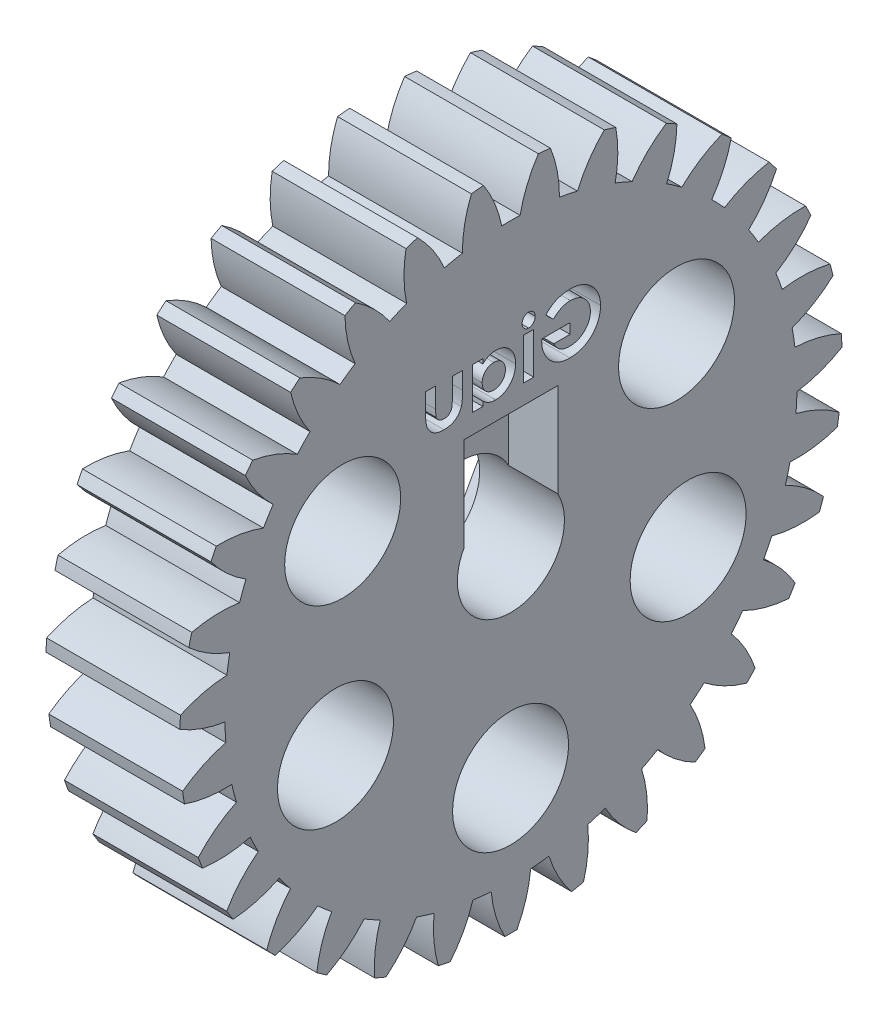
SolidWorks part; units mm, degrees
ref_plane "Plane1" through (0, 0, 0) normal (0, 0, 1) x (1, 0, 0)
ref_plane "Plane2" through (0, 0, 0) normal (0, 1, 0) x (1, 0, 0)
ref_plane "Plane3" through (0, 0, 0) normal (1, 0, 0) x (0, 0, -1)
sketch "HoldingSke" plane through (0, 0, 0) normal (0, 1, 0) x (1, 0, 0)
  line L0 (0, 0) -> (0.381, -0.2289)
  line L1 (-15, 0) -> (100, 0) construction
  line L2 (0, 0) -> (-2.1039, 2.3779)
  line L3 (0, 0) -> (-11.863, 4.5341)
  line L4 (0, 0) -> (7.4025, 4.4479)
  line L5 (0, 0) -> (-46.8476, -17.4728)
  line L6 (0, 0) -> (-12.4344, -8.3896)
  line L7 (-2.1039, 2.3779) -> (8.6586, 51.2059)
  line L8 (-76.2, 54.61) -> (-76.1, 54.61)
  line L9 (-71.009, 38.7566) -> (-53.1078, 45.2721)
  line L10 (-76.2, 71.12) -> (104.1128, 71.12)
  line L11 (0, 0) -> (-15, 0)
  line L12 (-76.2, 101.6) -> (-76.123, 101.6)
  line L13 (24.9733, 27.94) -> (52.9518, 28.4284)
  line L14 (24.9733, 27.94) -> (24.9743, 27.94)
  line L15 (24.9733, 27.94) -> (100.4006, 29.5858)
  line L16 (-63.627, -2.25) -> (-12.827, -2.25)
  circle A0 centre (0, 0) radius 0.4
  circle A1 centre (0, 0) radius 32.0615
  circle A2 centre (0, 0) radius 37.5
  circle A3 centre (0, 0) radius 0.4
  dimension "MHD" = 64.123
  dimension "Hub_dia" = 75
  dimension "Bore" = 0.8
  dimension "MBD" = 0.8
  dimension "Num_teeth" = 31
  dimension "Pitch_radius" = 180.3128
  dimension "Pitch" = 0.4444
  dimension "Width" = 15
  dimension "Overall_len" = 50
  dimension "Show_teeth" = 31
  dimension "Thickness" = 15
  dimension "OAL" = 50.0001
  dimension "T_dim" = 0.1
  dimension "Ap" = 20
  dimension "H" = 19.05
  dimension "Backlash" = 0.077
  dimension "Addendum_fac" = 1
  dimension "Dedendum_fac" = 1.25
  dimension "Clearance_fac" = 0.25
  dimension "Dedendum_add" = 0.001
  dimension "Module" = 2.25
sketch "BasProSke" plane through (0, 0, 0) normal (0, 1, 0) x (1, 0, 0)
  line L0 (-10, 0) -> (60, 0) construction
  line L1 (0, 0) -> (0, 37.125)
  line L2 (0, 0) -> (15, 0)
  line L3 (15, 0) -> (15, 37.125)
  line L4 (15, 37.125) -> (0, 37.125)
  dimension "Diameter" = 74.25
  dimension "Thickness" = 15
revolve "Base-Revolve" add sketch "BasProSke" angle 360 about L0
sketch "TooCutSke" plane through (0, 0, 0) normal (1, 0, 0) x (0, 0, -1)
  line L1 (0, 0) -> (0, 107) construction
  line L2 (0, 0) -> (-1.9011, 34.8231) construction
  line L3 (0, 0) -> (-7.0488, 69.3161) construction
  line L4 (-1.9011, 34.8231) -> (-3.5244, 34.6581) construction
  arc A0 (1.0309, 32.0449) -> (-1.0309, 32.0449) centre (0, 0) ccw
  arc A1 (3.0958, 37.0212) -> (-3.0958, 37.0212) centre (0, 0) ccw
  circle A2 centre (0, 0) radius 34.875 construction
  circle A3 centre (0, 0) radius 32.7718 construction
  arc A4 (-1.0309, 32.0449) -> (-3.0958, 37.0212) centre (-14.7056, 29.2871) ccw
  arc A5 (3.0958, 37.0212) -> (1.0309, 32.0449) centre (14.7056, 29.2871) ccw
  dimension "Root_dia" = 64.123
  dimension "Overcut_dia" = 74.3008
  dimension "Pitch_dia" = 69.75
  dimension "Base_dia" = 65.5436
  dimension "Flank_rad" = 13.95
  dimension "Half_ang" = 5.806
  dimension "Half_CT" = 1.6316
extrude "ToothCut" cut sketch "TooCutSke" along normal through all
fillet "Breaks" [suppressed] radius 0.045 tangent propagation no
fillet "RootFillets" [suppressed] radius 0.5635
pattern_circular "TeethCuts" count 31 over 360 about axis through (-10, 0, 0) along (1, 0, 0) of "ToothCut", "RootFillets", "Breaks"
sketch "HubNeaOneSke" plane through (0, 0, 0) normal (-1, 0, 0) x (0, 0, 1)
  circle A0 centre (0, 0) radius 32.0615
  dimension "Diameter" = 64.123
extrude "HubNearOne" [suppressed] add sketch "HubNeaOneSke" along normal blind 35.0001
sketch "HubNeaBotSke" plane through (0, 0, 0) normal (-1, 0, 0) x (0, 0, 1)
  circle A0 centre (0, 0) radius 32.0615
  dimension "Diameter" = 64.123
extrude "HubNearBoth" [suppressed] add sketch "HubNeaBotSke" along normal blind 17.5
ref_plane "FarPln" through (15, 0, 0) normal (1, 0, 0) x (0, 0, -1)
sketch "HubFarSke" plane through (15, 0, 0) normal (1, 0, 0) x (0, 0, -1)
  circle A0 centre (0, 0) radius 32.0615
  dimension "Diameter" = 64.123
extrude "HubFar" [suppressed] add sketch "HubFarSke" along normal blind 17.5
sketch "BorSke" plane through (0, 0, 0) normal (1, 0, 0) x (0, 0, -1)
  circle A0 centre (0, 0) radius 6
  dimension "Diameter" = 12
extrude "Bore" cut sketch "BorSke" along normal mid plane 100.0001
sketch "KeySke" plane through (0, 0, 0) normal (1, 0, 0) x (0, 0, -1)
  line L0 (-0.05, 0) -> (-0.05, 0.5)
  line L1 (-0.05, 0.5) -> (0.05, 0.5)
  line L2 (0.05, 0.5) -> (0.05, 0)
  line L3 (0, 0) -> (0, 34) construction
  line L4 (-0.05, 0) -> (0.05, 0)
  dimension "Offset" = 0.5
  dimension "Width" = 0.1
extrude "Keyway" [suppressed] cut sketch "KeySke" along normal mid plane 100.0001
pattern_circular "Keyway2" [suppressed] count 2 every 90 about axis through (-10, 0, 0) along (1, 0, 0)
sketch "Sketch1" plane through (0, 0, 0) normal (-1, 0, 0) x (0, 0, 1)
  text T0 "<b>Giau</b>\r\n\r\n" font "Century Gothic" height 6.35
sketch "Sketch2" plane through (15, 0, 0) normal (1, 0, 0) x (0, 0, -1)
  line L2 (-5.25, 2.9047) -> (-5.25, 13.4047)
  line L3 (-5.25, 13.4047) -> (5.25, 13.4047)
  line L4 (5.25, 2.9047) -> (5.25, 13.4047)
  arc A0 (-5.25, 2.9047) -> (5.25, 2.9047) centre (0, 0) ccw
  circle A1 centre (0, 0) radius 6 construction
  dimension "D1" = 0
  dimension "D5" = 10.5
  dimension "D6" = 10.5
extrude "Cut-Extrude1" cut sketch "Sketch2" against normal blind 5.5
extrude "Cut-Extrude3" cut sketch "Sketch1" against normal through all
sketch "Sketch7" plane through (0, 0, 0) normal (-1, 0, 0) x (0, 0, 1)
sketch "Sketch8" plane through (0, 0, 0) normal (-1, 0, 0) x (0, 0, 1)
  line L1 (13.854, -0.2947) -> (7.1504, 11.8322)
  line L2 (7.1504, 11.8322) -> (-6.7036, 12.0901)
  line L3 (-6.7036, 12.0901) -> (-13.854, 0.2211)
  line L4 (-13.854, 0.2211) -> (-7.1504, -11.9057)
  line L5 (-7.1504, -11.9057) -> (6.7036, -12.1637)
  line L6 (6.7036, -12.1637) -> (13.854, -0.2947)
  circle A0 centre (0, -0.0368) radius 12 construction
  circle A1 centre (0, 0) radius 6 construction
  dimension "D1" = 0
  dimension "D2" = 24
extrude "Cut-Extrude5" cut sketch "Sketch8" against normal blind 5.5
sketch "Sketch10" plane through (0, 0, 0) normal (-1, 0, 0) x (0, 0, 1)
  line L0 (-6.7036, 12.0901) -> (-13.854, 0.2211) construction
  line L1 (13.854, -0.2947) -> (7.1504, 11.8322) construction
  line L2 (6.7036, -12.1637) -> (13.854, -0.2947) construction
  line L3 (-7.1504, -11.9057) -> (6.7036, -12.1637) construction
  line L4 (-13.854, 0.2211) -> (-7.1504, -11.9057) construction
  circle A0 centre (-19.8634, -9.5779) radius 6.5
  circle A1 centre (0.0405, -22.0413) radius 6.5
  circle A2 centre (19.6658, -10.0262) radius 6.5
  circle A3 centre (18.8582, 11.3227) radius 6.5
  circle A4 centre (-18.5625, 11.7841) radius 6.5
  dimension "D6" = 13
  dimension "D7" = 13
  dimension "D8" = 13
  dimension "D9" = 13
  dimension "D10" = 13
  dimension "D1" = 10
  dimension "D2" = 10
  dimension "D3" = 10
  dimension "D4" = 10
  dimension "D5" = 10
extrude "Cut-Extrude6" cut sketch "Sketch10" against normal through all
equation "' \"Module@HoldingSke\" = 6.35"
equation "' \"Num_teeth@HoldingSke\" = 12"
equation "' \"Ap@HoldingSke\" =  20"
equation "' \"Width@HoldingSke\" = 0.5 * 25.4"
equation "' \"Hub_dia@HoldingSke\"= 1 * 25.4"
equation "' \"Overall_len@HoldingSke\" = 1.0 * 25.4"
equation "' \"Bore@HoldingSke\" = 0.75 * 25.4"
equation "' \"T_dim@HoldingSke\" = 0.1 * 25.4"
equation "' \"Width@KeySke\" = 0.25 * 25.4"
equation "' \"Show_teeth@HoldingSke\" = 13"
equation "' \"Backlash@HoldingSke\" = 0.009 * 25.4"
equation "' \"Addendum_fac@HoldingSke\" = 1.0"
equation "' \"Dedendum_fac@HoldingSke\" = 1.25"
equation "' \"Dedendum_add@HoldingSke\" = 0.00005 * 25.4"
equation "' \"Clearance_fac@HoldingSke\" = 0.25"
equation "\"Pitch@HoldingSke\" = 1 / \"Module@HoldingSke\""
equation "\"Overcut_dia@TooCutSke\" = (\"Num_teeth@HoldingSke\" + 2 * \"Addendum_fac@HoldingSke\") / \"Pitch@HoldingSke\" + 0.002 * 25.4"
equation "\"Pitch_dia@TooCutSke\" = \"Num_teeth@HoldingSke\" / \"Pitch@HoldingSke\""
equation "\"Base_dia@TooCutSke\" = \"Num_teeth@HoldingSke\" / \"Pitch@HoldingSke\" * cos((\"Ap@HoldingSke\"  * 3.14159265 / 180))"
equation "\"Root_dia@TooCutSke\" = (\"Num_teeth@HoldingSke\" + 2) / \"Pitch@HoldingSke\" - 2 * (\"Addendum_fac@HoldingSke\" + \"Dedendum_fac@HoldingSke\") / \"Pitch@HoldingSke\" - \"Dedendum_add@HoldingSke\" * 2"
equation "\"Half_ang@TooCutSke\" = 180 / \"Num_teeth@HoldingSke\""
equation "\"Half_CT@TooCutSke\" = \"Num_teeth@HoldingSke\" / \"Pitch@HoldingSke\" * sin((3.14159265 / 2 / \"Num_teeth@HoldingSke\")) / 2 - 7 * \"Backlash@HoldingSke\" / 4"
equation "\"Flank_rad@TooCutSke\" = \"Num_teeth@HoldingSke\" / \"Pitch@HoldingSke\" / 5"
equation "\"Radius@RootFillets\" = \"Clearance_fac@HoldingSke\" / \"Pitch@HoldingSke\" + \"Dedendum_add@HoldingSke\""
equation "\"Break_rad@Breaks\" = 0.02 / \"Pitch@HoldingSke\""
equation "\"Thickness@HoldingSke\" = \"Width@HoldingSke\""
equation "\"OAL@HoldingSke\" = \"Thickness@HoldingSke\""
equation "\"MHD@HoldingSke\" = (\"Num_teeth@HoldingSke\" + 2) / \"Pitch@HoldingSke\" - 2 * (\"Addendum_fac@HoldingSke\" + \"Dedendum_fac@HoldingSke\")  / \"Pitch@HoldingSke\" - \"Dedendum_add@HoldingSke\" * 2"
equation "\"MBD@HoldingSke\" = (\"Num_teeth@HoldingSke\" + 2) / \"Pitch@HoldingSke\" - 2 * (\"Addendum_fac@HoldingSke\" + \"Dedendum_fac@HoldingSke\")  / \"Pitch@HoldingSke\" - \"Dedendum_add@HoldingSke\" * 2 - 0.002 * 25.4"
equation "\"MHD@HoldingSke\" = ((sgn( \"MHD@HoldingSke\" - \"Hub_dia@HoldingSke\" )-1)*( \"MHD@HoldingSke\" - \"Hub_dia@HoldingSke\" ))/-2+ \"Hub_dia@HoldingSke\""
equation "\"MBD@HoldingSke\" = ((sgn( \"MBD@HoldingSke\" - \"Bore@HoldingSke\" )-1)*( \"MBD@HoldingSke\" - \"Bore@HoldingSke\" ))/-2+ \"Bore@HoldingSke\""
equation "\"OAL@HoldingSke\" = ((sgn( \"OAL@HoldingSke\" - \"Overall_len@HoldingSke\" )+1)*( \"OAL@HoldingSke\" - \"Overall_len@HoldingSke\" ))/2 + \"Overall_len@HoldingSke\" + 0.000002 * 25.4"
equation "\"Num_teeth@TeethCuts\" = int( \"Show_teeth@HoldingSke\" ) + 1"
equation "\"Num_teeth@TeethCuts\" = ((sgn( \"Num_teeth@TeethCuts\" - \"Num_teeth@HoldingSke\" )-1)*( \"Num_teeth@TeethCuts\" - \"Num_teeth@HoldingSke\" ))/-2+ \"Num_teeth@HoldingSke\""
equation "\"Num_teeth@TeethCuts\" = ((sgn( \"Num_teeth@TeethCuts\" - 2.0)+1)*( \"Num_teeth@TeethCuts\" - 2.0))/2 +2.0"
equation "\"Angle@TeethCuts\" = 360.0 / \"Num_teeth@HoldingSke\""
equation "\"Diameter@BasProSke\" = (\"Num_teeth@HoldingSke\" + 2 * \"Addendum_fac@HoldingSke\") / \"Pitch@HoldingSke\""
equation "\"Thickness@BasProSke\"  = \"Thickness@HoldingSke\""
equation "' \"Fillet_rad@BasProSke\" =  \"Thickness@HoldingSke\" * 0.05"
equation "\"MHD@HoldingSke\" = ((sgn( \"MHD@HoldingSke\" - \"Root_dia@TooCutSke\" )-1)*( \"MHD@HoldingSke\" - \"Root_dia@TooCutSke\" ))/-2+ \"Root_dia@TooCutSke\""
equation "\"Diameter@HubNeaOneSke\" = \"MHD@HoldingSke\""
equation "\"Length@HubNearOne\" = \"OAL@HoldingSke\" - \"Thickness@BasProSke\""
equation "\"Diameter@HubNeaBotSke\" = \"MHD@HoldingSke\""
equation "\"Length@HubNearBoth\" = ( \"OAL@HoldingSke\" - \"Thickness@BasProSke\" ) / 2.0"
equation "\"Thickness@FarPln\" = \"Thickness@BasProSke\""
equation "\"Diameter@HubFarSke\" = \"MHD@HoldingSke\""
equation "\"Length@HubFar\" = ( \"OAL@HoldingSke\" - \"Thickness@BasProSke\" ) / 2.0"
equation "\"Diameter@BorSke\"=12"
equation "\"D1@Bore\" = \"OAL@HoldingSke\" * 2.0"
equation "\"D1@Keyway\" = \"OAL@HoldingSke\" * 2.0"
equation "\"Offset@KeySke\" = \"T_dim@HoldingSke\" + \"MBD@HoldingSke\" / 2.0"
